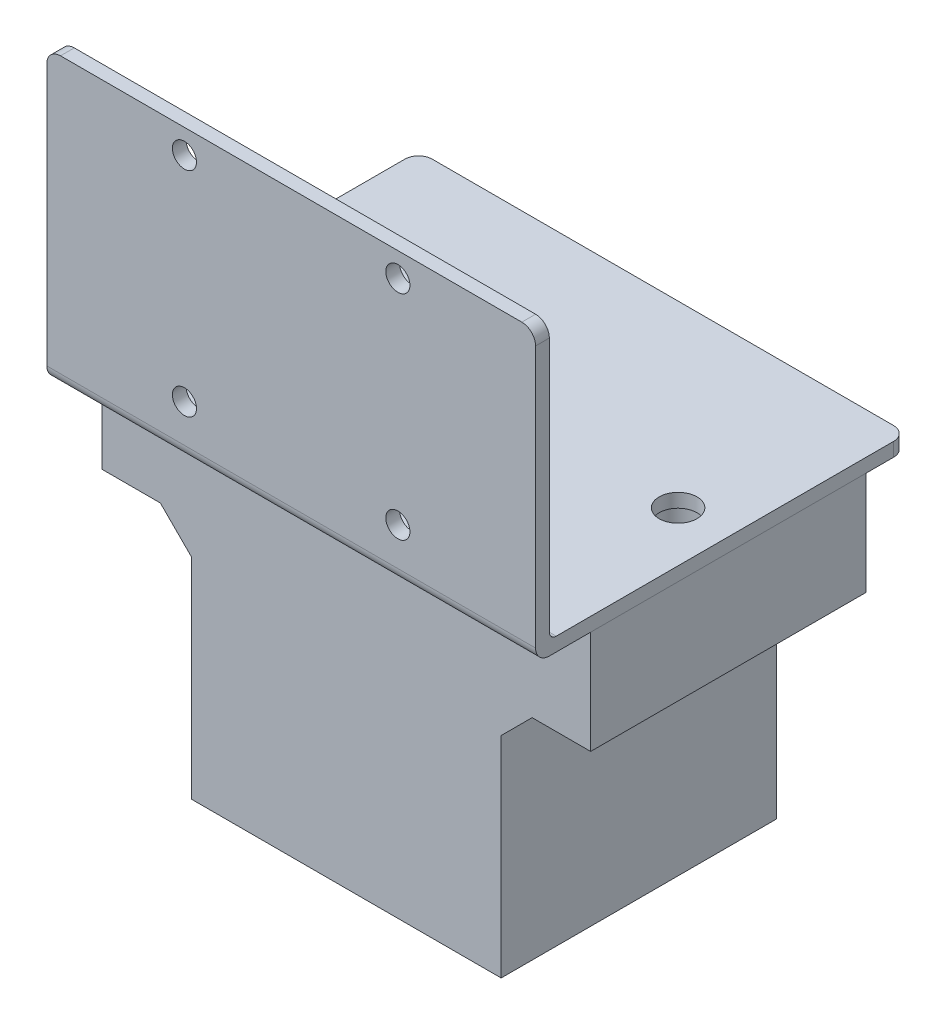
SolidWorks part; units mm, degrees
ref_plane "Plano frontal" through (0, 0, 0) normal (0, 0, 1) x (1, 0, 0)
ref_plane "Plano superior" through (0, 0, 0) normal (0, 1, 0) x (1, 0, 0)
ref_plane "Plano direito" through (0, 0, 0) normal (1, 0, 0) x (0, 0, -1)
sketch "Esboço1" plane through (0, 0, 0) normal (1, 0, 0) x (0, 0, -1)
  line L0 (0, 0) -> (0, 42)
  line L1 (0, 42) -> (2, 42)
  line L2 (2, 42) -> (2, 2)
  line L3 (2, 2) -> (54, 2)
  line L4 (54, 2) -> (54, 0)
  line L5 (54, 0) -> (0, 0)
  dimension "D1" = 42
  dimension "D2" = 54
  dimension "D3" = 2
extrude "Ressalto-extrusão1" add sketch "Esboço1" along normal mid plane 71
sketch "Esboço2" plane through (0, 2, 0) normal (0, 1, 0) x (1, 0, 0)
  line L0 (0, 0) -> (0, 54) construction
  line L1 (35.5, 0) -> (-35.5, 0) construction
  line L2 (35.5, 54) -> (-35.5, 54) construction
  line L3 (-35.5, 28) -> (35.5, 28) construction
  line L4 (-35.5, 54) -> (-35.5, 2) construction
  line L5 (35.5, 54) -> (35.5, 2) construction
  circle A0 centre (-27.5, 28) radius 2.75
  circle A1 centre (28.2, 28) radius 2.75
  dimension "D1" = 5.5
  dimension "D3" = 8
  dimension "D4" = 7.3
  dimension "D2" = 26
extrude "Corte-extrusão1" cut sketch "Esboço2" against normal through all and the other way through all
fillet "Filete1" radius 2 5 edges at (-35.5, 42, -1) (-35.5, 1, -54) (35.5, 42, -1) (35.5, 1, -54) (0, 0, 0)
fillet "Filete2" radius 1 1 edges at (0, 2, -2)
sketch "Esboço3" plane through (0, 0, -2) normal (0, 0, -1) x (-1, 0, 0)
  line L0 (0, 2) -> (0, 42) construction
  line L1 (-33.5, 2) -> (33.5, 2) construction
  line L2 (-33.5, 42) -> (33.5, 42) construction
  line L3 (35.5, 2) -> (-35.5, 2) construction
  line L4 (21, 44) -> (-21, 44) construction
  line L5 (21, 44) -> (21, 2) construction
  line L6 (21, 2) -> (-21, 2) construction
  line L7 (-21, 44) -> (-21, 2) construction
  line L8 (21, 44) -> (-21, 2) construction
  line L9 (21, 2) -> (-21, 44) construction
  line L11 (15.5, 7.5) -> (-15.5, 7.5) construction
  line L12 (15.5, 7.5) -> (15.5, 38.5) construction
  line L13 (15.5, 38.5) -> (-15.5, 38.5) construction
  line L14 (-15.5, 7.5) -> (-15.5, 38.5) construction
  line L15 (15.5, 7.5) -> (-15.5, 38.5) construction
  line L16 (15.5, 38.5) -> (-15.5, 7.5) construction
  circle A0 centre (-15.5, 38.5) radius 1.75
  circle A1 centre (15.5, 38.5) radius 1.75
  circle A2 centre (15.5, 7.5) radius 1.75
  circle A3 centre (-15.5, 7.5) radius 1.75
  point P6 (0, 23)
  point P13 (0, 23)
  point P28 (0, 23)
  dimension "D3" = 3.5
  dimension "D1" = 42
  dimension "D2" = 31
  dimension "D4" = 4
extrude "Corte-extrusão2" cut sketch "Esboço3" against normal through all
sketch "Esboço4" plane through (0, 0, 0) normal (0, -1, 0) x (1, 0, 0)
  line L0 (-35.5, -2) -> (-35.5, -52) construction
  line L1 (-35.5, -8) -> (35.5, -8)
  line L2 (-35.5, -8) -> (-35.5, -48)
  line L3 (-35.5, -48) -> (35.5, -48)
  line L4 (35.5, -8) -> (35.5, -48)
  line L5 (35.5, -2) -> (35.5, -52) construction
  line L6 (-27.5, -28) -> (28.2, -28) construction
  line L7 (0.35, -48) -> (0.35, -8) construction
  circle A0 centre (-27.5, -28) radius 3.25
  circle A1 centre (28.2, -28) radius 3.25
  point P15 (0.35, -28)
  dimension "D2" = 6.5
  dimension "D1" = 40
extrude "Ressalto-extrusão2" add sketch "Esboço4" along normal blind 15 separate body
sketch "Esboço5" plane through (0, -15, 0) normal (0, -1, 0) x (1, 0, 0)
  line L0 (35.5, -8) -> (-35.5, -8) construction
  line L1 (-22.5, -8) -> (22.5, -8)
  line L2 (-22.5, -8) -> (-22.5, -48)
  line L3 (-22.5, -48) -> (22.5, -48)
  line L4 (22.5, -8) -> (22.5, -48)
  line L5 (-35.5, -48) -> (35.5, -48) construction
  line L6 (-35.5, -28) -> (-22.5, -28) construction
  line L7 (-35.5, -8) -> (-35.5, -48) construction
  line L8 (22.5, -28) -> (35.5, -28) construction
  line L9 (35.5, -48) -> (35.5, -8) construction
  line L10 (0, -8) -> (0, -48) construction
  line L12 (-17.875, -40.625) -> (17.875, -40.625)
  line L13 (-17.875, -40.625) -> (-17.875, -15.375)
  line L14 (-17.875, -15.375) -> (17.875, -15.375)
  line L15 (17.875, -40.625) -> (17.875, -15.375)
  line L16 (-17.875, -40.625) -> (17.875, -15.375) construction
  line L17 (-17.875, -15.375) -> (17.875, -40.625) construction
  point P18 (0, -28)
  dimension "D1" = 45
  dimension "D2" = 25.25
  dimension "D3" = 35.75
extrude "Ressalto-extrusão3" add sketch "Esboço5" along normal blind 35
chamfer "Chanfro1" distance 4.5 angle 45 2 edges at (-22.5, -15, -28) (22.5, -15, -28)
